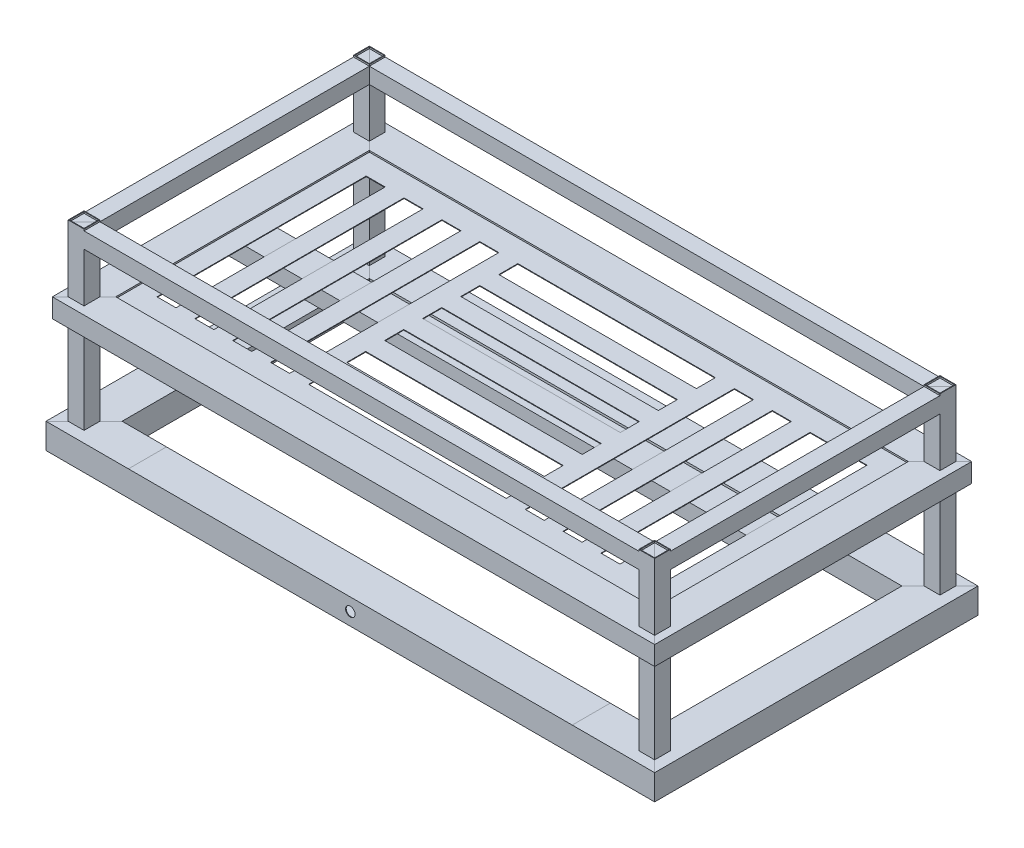
SolidWorks part; units mm, degrees
other "Markup2"
sketch "Sketch9" plane through (-960, -40, 510) normal (0, 0, 1) x (1, 0, 0)
other "DetailItem2"
other "DetailItem3"
other "DetailItem4"
other "DetailItem5"
other "DetailItem6"
other "Markup3"
sketch "Sketch10" plane through (960, 590, 510) normal (0.1315, 0.1279, 0.983) x (0.9913, -0.0123, -0.131)
material "1060 Alloy"
ref_plane "Front Plane" through (0, 0, 0) normal (0, 0, 1) x (1, 0, 0)
ref_plane "Top Plane" through (0, 0, 0) normal (0, 1, 0) x (1, 0, 0)
ref_plane "Right Plane" through (0, 0, 0) normal (1, 0, 0) x (0, 0, -1)
sketch "Sketch1" plane through (0, 0, 0) normal (0, 1, 0) x (1, 0, 0)
  line L0 (-700, -450) -> (-900, -450)
  line L1 (-900, -450) -> (-900, 450)
  line L2 (-900, 450) -> (900, 450)
  line L3 (900, 450) -> (900, -450)
  line L4 (900, -450) -> (700, -450)
  point P3 (0, 450)
  point P8 (900, 0)
  dimension "D1" = 200
  dimension "D2" = 1800
  dimension "D3" = 900
sketch3d "3DSketch2"
  line L13 (-700, -40, 510) -> (-700, 40, 510)
  line L14 (-700, -40, 510) -> (-700, -40, 390)
  line L15 (-700, -40, 390) -> (-700, 40, 390)
  line L16 (-700, 40, 510) -> (-700, 40, 390)
  line L17 (-700, -40, 510) -> (-700, 40, 390) construction
  line L18 (-700, -40, 390) -> (-700, 40, 510) construction
  line L23 (-700, 22.7418, 484.1127) -> (-700, -36.8775, 394.6837) construction
  line L24 (-700, 29.8097, 405.2855) -> (-700, -29.8097, 494.7145) construction
  line L25 (-900, 0, 450) -> (-900, 0, -450) construction
  point P0 (-700, 0, 450)
  point P6 (-700, 0, 450)
  dimension "D1" = 80
  dimension "D2" = 120
sweep "Sweep2" add profiles "3DSketch2" path "Sketch1"
sketch "Sketch2" plane through (-700, 0.0001, 0) normal (1, 0, 0) x (0, 0, -1)
  line L0 (510, 40.0001) -> (-510, 40.0001) construction
  line L1 (-392, 38.0001) -> (-508, 38.0001)
  line L2 (-392, 38.0001) -> (-392, -37.9999)
  line L3 (-392, -37.9999) -> (-508, -37.9999)
  line L4 (-508, 38.0001) -> (-508, -37.9999)
  line L5 (-392, 38.0001) -> (-508, -37.9999) construction
  line L6 (-392, -37.9999) -> (-508, 38.0001) construction
  line L7 (-510, 40.0001) -> (-510, -39.9999) construction
  point P0 (-450, 0.0001)
  dimension "D1" = 116
  dimension "D2" = 76
  dimension "D3" = 2
  dimension "D4" = 2
sweep "Cut-Sweep1" cut profiles "Sketch2" path "Sketch1<3>"
sketch "Sketch1<3>" plane through (0, 0, 0) normal (0, 1, 0) x (1, 0, 0) same geometry as "Sketch1"
sketch "Sketch3" plane through (0, 40, 0) normal (0, 1, 0) x (1, 0, 0)
  line L0 (840, -390) -> (960, -510) construction
  line L1 (925, -425) -> (875, -425)
  line L2 (925, -425) -> (925, -475)
  line L3 (925, -475) -> (875, -475)
  line L4 (875, -425) -> (875, -475)
  line L5 (925, -425) -> (875, -475) construction
  line L6 (925, -475) -> (875, -425) construction
  line L7 (923, 473) -> (923, 427)
  line L8 (923, -427) -> (877, -427)
  line L9 (923, -427) -> (923, -473)
  line L10 (923, -473) -> (877, -473)
  line L11 (877, -427) -> (877, -473)
  line L12 (923, -427) -> (877, -473) construction
  line L13 (923, -473) -> (877, -427) construction
  line L14 (923, 473) -> (877, 473)
  line L15 (877, 473) -> (877, 427)
  line L16 (923, 427) -> (877, 427)
  line L17 (925, 475) -> (875, 475)
  line L18 (875, 475) -> (875, 425)
  line L19 (925, 425) -> (875, 425)
  line L20 (925, 475) -> (925, 425)
  line L21 (-877, 473) -> (-877, 427)
  line L22 (-877, 473) -> (-923, 473)
  line L23 (-923, 473) -> (-923, 427)
  line L24 (-877, 427) -> (-923, 427)
  line L25 (-875, 475) -> (-925, 475)
  line L26 (-925, 475) -> (-925, 425)
  line L27 (-875, 425) -> (-925, 425)
  line L28 (-875, 475) -> (-875, 425)
  line L29 (-877, -427) -> (-877, -473)
  line L30 (-877, -427) -> (-923, -427)
  line L31 (-923, -427) -> (-923, -473)
  line L32 (-877, -473) -> (-923, -473)
  line L33 (-875, -425) -> (-925, -425)
  line L34 (-925, -425) -> (-925, -475)
  line L35 (-875, -475) -> (-925, -475)
  line L36 (-875, -425) -> (-875, -475)
  point P0 (900, -450)
  point P7 (900, -450)
  dimension "D1" = 50
  dimension "D2" = 50
  dimension "D3" = 46
  dimension "D4" = 2
  dimension "D5" = 2
extrude "Boss-Extrude1" add sketch "Sketch3" along normal blind 550
ref_plane "Plane1" through (0, 560, 0) normal (0, 1, 0) x (1, 0, 0)
sketch "Sketch4" plane through (0, 560, 0) normal (0, 1, 0) x (1, 0, 0)
  line L0 (-877, -427) -> (-923, -473) construction
  line L1 (900, 450) -> (-900, 450)
  line L2 (900, 450) -> (900, -450)
  line L3 (900, -450) -> (-900, -450)
  line L4 (-900, 450) -> (-900, -450)
  line L5 (900, 450) -> (-900, -450) construction
  line L6 (900, -450) -> (-900, 450) construction
  point P0 (0, 0)
sketch3d "3DSketch3"
  line L5 (-911.5676, 520.3101, 450) -> (-926.5407, 468.9356, 450) construction
  line L6 (-969.6491, 533.6905, 450) -> (-958.3492, 537.9589, 450) construction
  line L7 (-875, 585, 450) -> (-925, 585, 450)
  line L8 (-875, 585, 450) -> (-875, 535, 450)
  line L9 (-875, 535, 450) -> (-925, 535, 450)
  line L10 (-925, 585, 450) -> (-925, 535, 450)
  line L11 (-875, 585, 450) -> (-925, 535, 450) construction
  line L12 (-875, 535, 450) -> (-925, 585, 450) construction
  point P0 (-900, 560, 450)
  point P6 (-900, 560, 450)
  dimension "D1" = 50
  dimension "D2" = 50
  dimension "D3" = 76
  dimension "D4" = 50
sweep "Sweep4" add profiles "3DSketch3" path "Sketch4"
sketch3d "3DSketch4"
  line L1 (-877, 583, 450) -> (-923, 583, 450)
  line L2 (-877, 583, 450) -> (-877, 537, 450)
  line L3 (-877, 537, 450) -> (-923, 537, 450)
  line L4 (-923, 583, 450) -> (-923, 537, 450)
  line L5 (-877, 583, 450) -> (-923, 537, 450) construction
  line L6 (-877, 537, 450) -> (-923, 583, 450) construction
  point P0 (-900, 560, 450)
  dimension "D1" = 46
  dimension "D2" = 46
sweep "Cut-Sweep2" cut profiles "3DSketch4" path "Sketch4<2>"
sketch "Sketch4<2>" plane through (0, 560, 0) normal (0, 1, 0) x (1, 0, 0) same geometry as "Sketch4"
ref_plane "Plane2" through (0, 350, 0) normal (0, 1, 0) x (1, 0, 0)
sketch "Sketch5" plane through (0, 350, 0) normal (0, 1, 0) x (1, 0, 0)
  line L1 (900, 450) -> (-900, 450)
  line L2 (900, 450) -> (900, -450)
  line L3 (900, -450) -> (-900, -450)
  line L4 (-900, 450) -> (-900, -450)
  line L5 (900, 450) -> (-900, -450) construction
  line L6 (900, -450) -> (-900, 450) construction
  point P0 (0, 0)
  dimension "D1" = 900
  dimension "D2" = 1800
sketch3d "3DSketch5"
  line L1 (-850, 380, 450) -> (-950, 380, 450)
  line L2 (-850, 380, 450) -> (-850, 320, 450)
  line L3 (-850, 320, 450) -> (-950, 320, 450)
  line L4 (-950, 380, 450) -> (-950, 320, 450)
  line L5 (-850, 380, 450) -> (-950, 320, 450) construction
  line L6 (-850, 320, 450) -> (-950, 380, 450) construction
  point P0 (-900, 350, 450)
  dimension "D1" = 100
  dimension "D2" = 60
sweep "Sweep5" add profiles "3DSketch5" path "Sketch5"
sketch3d "3DSketch6"
  line L1 (-852, 378, 450) -> (-948, 378, 450)
  line L2 (-852, 378, 450) -> (-852, 322, 450)
  line L3 (-852, 322, 450) -> (-948, 322, 450)
  line L4 (-948, 378, 450) -> (-948, 322, 450)
  line L5 (-852, 378, 450) -> (-948, 322, 450) construction
  line L6 (-852, 322, 450) -> (-948, 378, 450) construction
  point P0 (-900, 350, 450)
  dimension "D1" = 96
  dimension "D2" = 56
sweep "Cut-Sweep3" cut profiles "3DSketch6" path "Sketch5<2>"
sketch "Sketch5<2>" plane through (0, 350, 0) normal (0, 1, 0) x (1, 0, 0) same geometry as "Sketch5"
sketch "Sketch6" plane through (0, 380, 0) normal (0, 1, 0) x (1, 0, 0)
  line L1 (850, 400) -> (-850, 400)
  line L2 (850, 400) -> (850, -400)
  line L3 (850, -400) -> (-850, -400)
  line L4 (-850, 400) -> (-850, -400)
  line L5 (850, 400) -> (-850, -400) construction
  line L6 (850, -400) -> (-850, 400) construction
  point P0 (0, 0)
extrude "Boss-Extrude3" add sketch "Sketch6" against normal blind 2 from offset 5 offset against normal yes
sketch "Sketch7" plane through (0, 375, 0) normal (0, 1, 0) x (1, 0, 0)
  line L0 (-850, 400) -> (850, 400) construction
  line L1 (-790, 330) -> (-730, 330)
  line L2 (-790, 330) -> (-790, -330)
  line L3 (-790, -330) -> (-730, -330)
  line L4 (-730, 330) -> (-730, -330)
  line L5 (-850, -400) -> (-850, 400) construction
  line L6 (-850, -400) -> (850, -400) construction
  line L7 (-670.522, 330) -> (-670.522, -330)
  line L8 (-670.522, 330) -> (-610.522, 330)
  line L9 (-610.522, 330) -> (-610.522, -330)
  line L10 (-670.522, -330) -> (-610.522, -330)
  line L11 (-551.044, 330) -> (-551.044, -330)
  line L12 (-551.044, 330) -> (-491.044, 330)
  line L13 (-491.044, 330) -> (-491.044, -330)
  line L14 (-551.044, -330) -> (-491.044, -330)
  line L15 (-431.566, 330) -> (-431.566, -330)
  line L16 (-431.566, 330) -> (-371.566, 330)
  line L17 (-371.566, 330) -> (-371.566, -330)
  line L18 (-431.566, -330) -> (-371.566, -330)
  line L19 (0, 654.8485) -> (0, -644.5034) construction
  line L20 (790, -330) -> (730, -330)
  line L21 (730, 330) -> (730, -330)
  line L22 (790, 330) -> (730, 330)
  line L23 (790, 330) -> (790, -330)
  line L24 (670.522, 330) -> (610.522, 330)
  line L25 (610.522, 330) -> (610.522, -330)
  line L26 (670.522, -330) -> (610.522, -330)
  line L27 (670.522, 330) -> (670.522, -330)
  line L28 (551.044, 330) -> (491.044, 330)
  line L29 (491.044, 330) -> (491.044, -330)
  line L30 (551.044, -330) -> (491.044, -330)
  line L31 (551.044, 330) -> (551.044, -330)
  line L32 (431.566, 330) -> (371.566, 330)
  line L33 (371.566, 330) -> (371.566, -330)
  line L34 (431.566, -330) -> (371.566, -330)
  line L35 (431.566, 330) -> (431.566, -330)
  line L37 (-311.566, 330) -> (311.566, 330)
  line L38 (-311.566, 330) -> (-311.566, 270)
  line L39 (-311.566, 270) -> (311.566, 270)
  line L40 (311.566, 330) -> (311.566, 270)
  line L41 (-311.566, 210) -> (-311.566, 150)
  line L42 (-311.566, 210) -> (311.566, 210)
  line L43 (311.566, 210) -> (311.566, 150)
  line L44 (-311.566, 150) -> (311.566, 150)
  line L46 (-311.566, 90) -> (-311.566, 30)
  line L47 (-311.566, 90) -> (311.566, 90)
  line L48 (311.566, 90) -> (311.566, 30)
  line L49 (-311.566, 30) -> (311.566, 30)
  line L51 (-311.566, -30) -> (-311.566, -90)
  line L52 (-311.566, -30) -> (311.566, -30)
  line L53 (311.566, -30) -> (311.566, -90)
  line L54 (-311.566, -90) -> (311.566, -90)
  line L56 (-311.566, -150) -> (-311.566, -210)
  line L57 (-311.566, -150) -> (311.566, -150)
  line L58 (311.566, -150) -> (311.566, -210)
  line L59 (-311.566, -210) -> (311.566, -210)
  line L61 (-311.566, -270) -> (-311.566, -330)
  line L62 (-311.566, -270) -> (311.566, -270)
  line L63 (311.566, -270) -> (311.566, -330)
  line L64 (-311.566, -330) -> (311.566, -330)
  line L65 (-431.566, 210) -> (-371.566, 210) [skipped]
  line L66 (-431.566, 90) -> (-371.566, 90) [skipped]
  line L67 (-431.566, -30) -> (-371.566, -30) [skipped]
  line L68 (-431.566, -150) -> (-371.566, -150) [skipped]
  line L69 (-431.566, -270) -> (-371.566, -270) [skipped]
  dimension "D1" = 70
  dimension "D2" = 60
  dimension "D3" = 70
  dimension "D4" = 60
  dimension "D6" = 60
  dimension "D7" = 60
  dimension "D8" = 60
  dimension "D5" = 4
  dimension "D9" = 6
extrude "Cut-Extrude1" cut sketch "Sketch7" against normal blind 127
sketch "Sketch11" plane through (850, 0, 0) normal (-1, 0, 0) x (0, 0, 1)
  line L0 (-400, 320) -> (400, 320) construction
  line L1 (-50, 320) -> (50, 320)
  line L2 (-50, 320) -> (-50, 373)
  line L3 (-50, 373) -> (50, 373)
  line L4 (50, 320) -> (50, 373)
  line L5 (400, 373) -> (-400, 373) construction
  line L7 (48, 371) -> (-48, 371)
  line L8 (48, 371) -> (48, 322)
  line L9 (48, 322) -> (-48, 322)
  line L10 (-48, 371) -> (-48, 322)
  line L11 (48, 371) -> (-48, 322) construction
  line L12 (48, 322) -> (-48, 371) construction
  point P8 (0, 320)
  point P10 (0, 346.5)
  dimension "D1" = 100
  dimension "D2" = 96
  dimension "D3" = 49
  dimension "D4" = 2
  dimension "D5" = 2
extrude "Boss-Extrude4" add sketch "Sketch11" along normal up to next
sketch "Sketch13" plane through (0, 0, 500) normal (0, 0, 1) x (1, 0, 0)
  line L0 (0, -100.5293) -> (0, 677.4267) construction
sketch "Sketch14" plane through (-700, 0.0001, 0) normal (1, 0, 0) x (0, 0, -1)
  line L1 (-392, 38.0001) -> (-508, 38.0001)
  line L2 (-392, 38.0001) -> (-392, -37.9999)
  line L3 (-392, -37.9999) -> (-508, -37.9999)
  line L4 (-390, 39.9999) -> (-510, 39.9999)
  line L5 (-510, 39.9999) -> (-510, -40.0001)
  line L6 (-510, -40.0001) -> (-390, -40.0001)
  line L7 (-390, -40.0001) -> (-390, 39.9999)
  line L8 (-390, 39.9999) -> (-510, 39.9999)
  line L9 (-510, 39.9999) -> (-510, -40.0001)
  line L10 (-510, -40.0001) -> (-390, -40.0001)
  line L11 (-390, -40.0001) -> (-390, 39.9999)
  line L12 (-508, 38.0001) -> (-508, -37.9999)
  dimension "D1" = 0
extrude "Boss-Extrude5" add sketch "Sketch14" along normal up to surface (1400 mm away) up to face at (700, 0, 450)
sketch "Sketch15" plane through (0, 0, 510) normal (0, 0, 1) x (1, 0, 0)
  circle A0 centre (0, 0) radius 15
  dimension "D1" = 30
extrude "Cut-Extrude2" cut sketch "Sketch15" against normal blind 5
